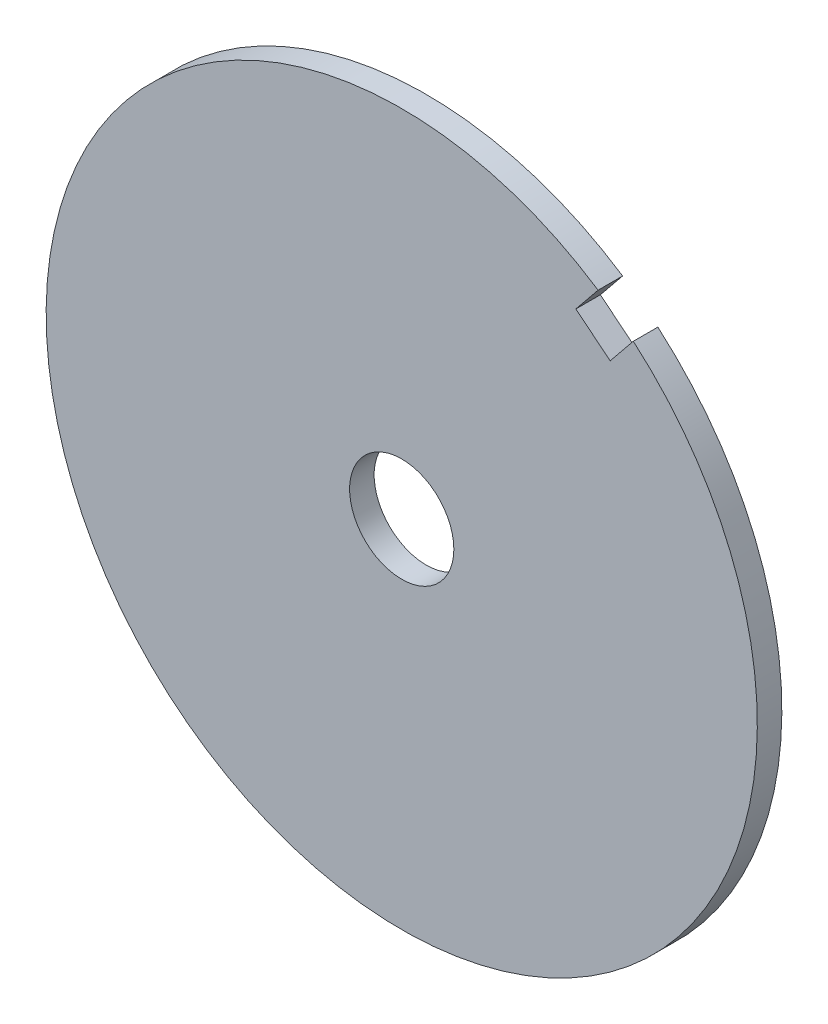
SolidWorks part; units mm, degrees
ref_plane "Front Plane" through (0, 0, 0) normal (0, 0, 1) x (1, 0, 0)
ref_plane "Top Plane" through (0, 0, 0) normal (0, 1, 0) x (1, 0, 0)
ref_plane "Right Plane" through (0, 0, 0) normal (1, 0, 0) x (0, 0, -1)
sketch "Sketch1" plane through (0, 0, 3372.7778) normal (0, 0, 1) x (1, 0, 0)
  circle A0 centre (0, 0) radius 92.075
  dimension "D1" = 184.15
extrude "Boss-Extrude1" add sketch "Sketch1" along normal blind 6.35
sketch "Sketch2" plane through (0, 0, 3379.1278) normal (0, 0, 1) x (1, 0, 0)
  circle A0 centre (0, 0) radius 13.4938
  dimension "D1" = 26.9875
extrude "Cut-Extrude1" cut sketch "Sketch2" against normal up to next
sketch "Sketch3" plane through (0, 0, 3379.1278) normal (0, 0, 1) x (1, 0, 0)
  line L0 (50.8455, 76.7629) -> (45.0925, 69.6737)
  line L1 (45.0925, 69.6737) -> (53.9677, 62.4712)
  line L2 (53.9677, 62.4712) -> (59.9697, 69.8673)
  line L3 (147.6389, 192.0065) -> (76.0966, 103.8479) construction
  line L4 (81.0273, 99.8465) -> (152.5696, 188.0051) construction
  circle A0 centre (0, 0) radius 92.075 construction
  dimension "D1" = 2.54
  dimension "D2" = 2.54
  dimension "D3" = 9.525
extrude "Cut-Extrude2" cut sketch "Sketch3" against normal through all and the other way through all
